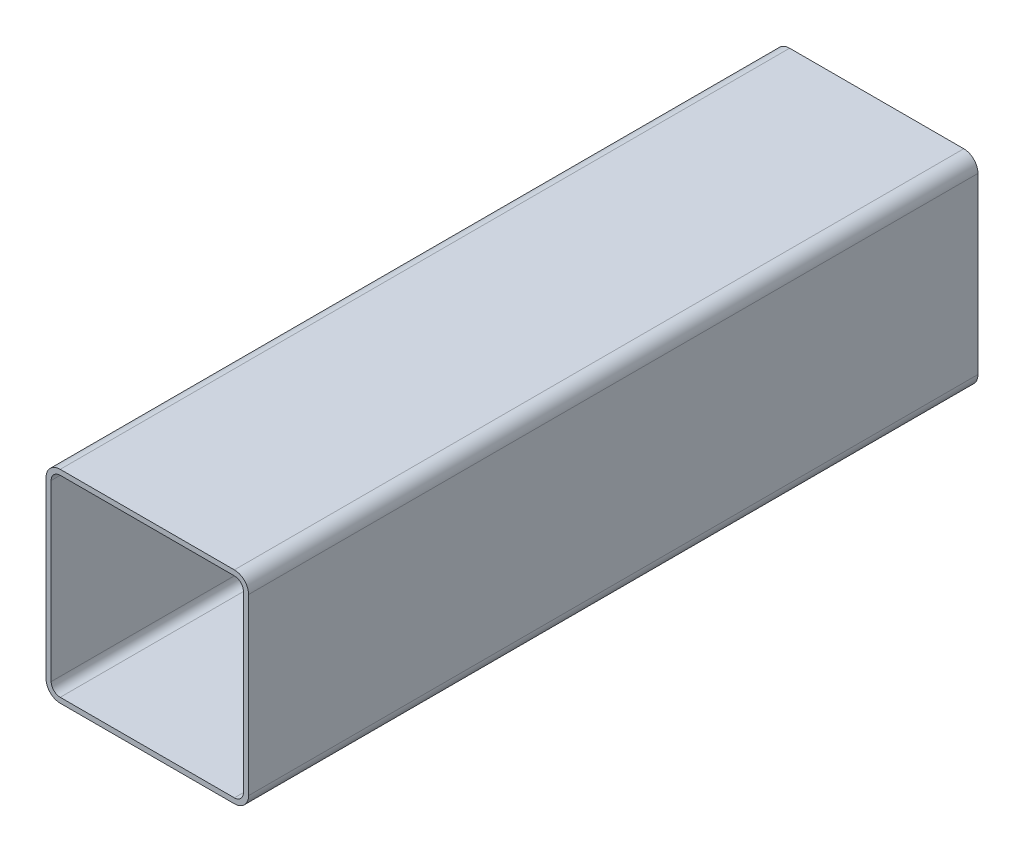
SolidWorks part; units mm, degrees
note: '?' marks a value the reader was unsure of.
material "Carbon Fiber, Plain Weave"
ref_plane "Front Plane" through (0, 0, 0) normal (0, 0, 1) x (1, 0, 0)
ref_plane "Top Plane" through (0, 0, 0) normal (0, 1, 0) x (1, 0, 0)
ref_plane "Right Plane" through (0, 0, 0) normal (1, 0, 0) x (0, 0, -1)
ref_axis "Axis1" through (0, 0, -88.99) along (0, 0, 1)?
ref_axis "Axis2" through (0, -55, 0) along (0, 1, 0)?
ref_axis "Axis3" through (-88.99, 0, 0) along (1, 0, 0)?
sketch "Sketch1" plane through (0, 0, 0) normal (0, 1, 0) x (1, 0, 0)
  line L0 (0, 0) -> (0, 304.8)
  dimension "D1" = 304.8
other "Structural Member1" corner treatment miter
ref_plane "Plane1" through (0, 0, 0) normal (0, 0, -1) x (-1, 0, 0)
sketch "Sketch137" plane through (0, 0, 0) normal (0, 0, -1) x (-1, 0, 0)
  line L0 (-42.3291, 36.3855) -> (-42.3291, -36.3855)
  line L1 (-36.3855, -42.3291) -> (36.3855, -42.3291)
  line L2 (-36.3855, 42.3291) -> (36.3855, 42.3291)
  line L3 (42.3291, 36.3855) -> (42.3291, -36.3855)
  line L4 (-42.3291, 42.3291) -> (42.3291, -42.3291) construction
  line L5 (-40.1701, 36.3855) -> (-40.1701, -36.3855)
  line L6 (-36.3855, -40.1701) -> (36.3855, -40.1701)
  line L7 (40.1701, 36.3855) -> (40.1701, -36.3855)
  line L8 (-36.3855, 40.1701) -> (36.3855, 40.1701)
  arc A0 (-42.3291, -36.3855) -> (-36.3855, -42.3291) centre (-36.3855, -36.3855) ccw
  arc A1 (36.3855, -42.3291) -> (42.3291, -36.3855) centre (36.3855, -36.3855) ccw
  arc A2 (36.3855, 42.3291) -> (42.3291, 36.3855) centre (36.3855, 36.3855) cw
  arc A3 (-42.3291, 36.3855) -> (-36.3855, 42.3291) centre (-36.3855, 36.3855) cw
  arc A4 (-40.1701, -36.3855) -> (-36.3855, -40.1701) centre (-36.3855, -36.3855) ccw
  arc A5 (36.3855, -40.1701) -> (40.1701, -36.3855) centre (36.3855, -36.3855) ccw
  arc A6 (36.3855, 40.1701) -> (40.1701, 36.3855) centre (36.3855, 36.3855) cw
  arc A7 (-40.1701, 36.3855) -> (-36.3855, 40.1701) centre (-36.3855, 36.3855) cw
  point P6 (-42.3291, -42.3291)
  point P28 (0, 0)
  dimension "CORNER_RADIUS" = 5.9436
  dimension "THICKNESS" = 2.159
  dimension "VERT LEG" = 84.6582
  dimension "HORZ LEG" = 84.6582
sketch "Sketch12" plane through (0, 42.3291, 0) normal (0, 1, 0) x (1, 0, 0)
  line L0 (0, 0) -> (0, 475) construction
  line L2 (-0.025, 436.65) -> (0.025, 436.65)
  line L3 (-3.2, 439.825) -> (-3.2, 510.175)
  line L4 (-0.025, 513.35) -> (0.025, 513.35)
  line L5 (3.2, 439.825) -> (3.2, 510.175)
  line L6 (-3.2, 436.65) -> (3.2, 513.35) construction
  line L7 (-3.2, 513.35) -> (3.2, 436.65) construction
  circle A0 centre (0, 475) radius 7.5 construction
  arc A1 (-0.025, 436.65) -> (-3.2, 439.825) centre (-0.025, 439.825) cw
  arc A2 (0.025, 436.65) -> (3.2, 439.825) centre (0.025, 439.825) ccw
  arc A3 (0.025, 513.35) -> (3.2, 510.175) centre (0.025, 510.175) cw
  arc A4 (-3.2, 510.175) -> (-0.025, 513.35) centre (-0.025, 510.175) cw
  dimension "D1" = 15
  dimension "D2" = 475
  dimension "D3" = 3.175
  dimension "D4" = 76.7
  dimension "D5" = 6.4
extrude "Cut-Extrude1" [suppressed] cut sketch "Sketch12" against normal up to next
hole_wizard "M5 Clearance Hole1" [suppressed] positions "Sketch14" profile "Sketch13" hole size "M5" standard "ANSI Metric"
sketch "Sketch14" plane through (42.3291, 0, 0) normal (-1, 0, 0) x (0, 0, 1)
  line L0 (0, 0) -> (-368.9375, 0) construction
  line L3 (-500, 21.8852) -> (-500, -22.8005) construction
  point P0 (-368.9375, 20)
  point P8 (-368.9375, -20)
  point P16 (-631.0625, -20)
  point P17 (-631.0625, 20)
  dimension "D1" = 40
  dimension "D2" = 500
  dimension "D3" = 262.125
sketch "Sketch13" plane through (42.3291, 20, -368.9375) normal (0, 1, 0) x (0, 0, -1)
  line L0 (0, 0) -> (0, 84.6582)
  line L1 (0, 84.6582) -> (2.75, 84.6582)
  line L2 (2.75, 84.6582) -> (2.75, 0)
  line L5 (2.75, 0) -> (0, 0)
  line L11 (0, -6.35) -> (0, 107.95) construction
  dimension "Thru Hole Dia." = 5.5
  dimension "Thru Hole Depth" = 84.6582
sketch "Sketch15" plane through (0, -42.3291, 0) normal (0, -1, 0) x (1, 0, 0)
  line L0 (0, -304.8) -> (0, -104.8) construction
  line L1 (36.3855, -304.8) -> (-36.3855, -304.8) construction
  line L3 (-0.025, -143.15) -> (0.025, -143.15)
  line L4 (-3.2, -139.975) -> (-3.2, -69.625)
  line L5 (-0.025, -66.45) -> (0.025, -66.45)
  line L6 (3.2, -139.975) -> (3.2, -69.625)
  line L7 (-3.2, -143.15) -> (3.2, -66.45) construction
  line L8 (-3.2, -66.45) -> (3.2, -143.15) construction
  circle A0 centre (0, -104.8) radius 7.5 construction
  arc A1 (-0.025, -143.15) -> (-3.2, -139.975) centre (-0.025, -139.975) cw
  arc A2 (0.025, -143.15) -> (3.2, -139.975) centre (0.025, -139.975) ccw
  arc A3 (0.025, -66.45) -> (3.2, -69.625) centre (0.025, -69.625) cw
  arc A4 (-3.2, -69.625) -> (-0.025, -66.45) centre (-0.025, -69.625) cw
  dimension "D1" = 15
  dimension "D3" = 3.175
  dimension "D2" = 200
  dimension "D4" = 6.4
  dimension "D5" = 76.7
extrude "Cut-Extrude2" [suppressed] cut sketch "Sketch15" against normal up to next
sketch "Sketch111" plane through (0, -42.3291, 0) normal (0, -1, 0) x (-1, 0, 0)
  line L0 (0, 65) -> (0, 0) construction
  line L1 (-11, 120) -> (11, 120)
  line L2 (-16, 115) -> (-16, 15)
  line L3 (-11, 10) -> (11, 10)
  line L4 (16, 115) -> (16, 15)
  line L5 (-16, 120) -> (16, 10) construction
  line L6 (-16, 10) -> (16, 120) construction
  arc A0 (11, 10) -> (16, 15) centre (11, 15) ccw
  arc A1 (-16, 15) -> (-11, 10) centre (-11, 15) ccw
  arc A2 (-11, 120) -> (-16, 115) centre (-11, 115) ccw
  arc A3 (11, 120) -> (16, 115) centre (11, 115) cw
  point P0 (0, 65)
  dimension "D4" = 5
  dimension "D1" = 65
  dimension "D2" = 32
  dimension "D3" = 110
extrude "Cut-Extrude3" [suppressed] cut sketch "Sketch111" against normal up to next
hole_wizard "M5 Clearance Hole2" [suppressed] positions "Sketch122" profile "Sketch121" hole size "M5" standard "ANSI Metric"
sketch "Sketch122" plane through (42.3291, 0, 0) normal (1, 0, 0) x (0, 0, -1)
  line L0 (0, 0) -> (28.3774, 0) construction
  line L3 (0, -36.3855) -> (0, 36.3855) construction
  point P0 (10, -27.5)
  point P11 (50, -27.5)
  point P13 (90, -27.5)
  point P16 (90, 27.5)
  point P17 (50, 27.5)
  point P18 (10, 27.5)
  dimension "D1" = 55
  dimension "D2" = 10
  dimension "D3" = 40
  dimension "D4" = 40
sketch "Sketch121" plane through (42.3291, -27.5, -10) normal (0, 1, 0) x (0, 0, -1)
  line L0 (0, 0) -> (0, 84.6582)
  line L1 (0, 84.6582) -> (2.75, 84.6582)
  line L2 (2.75, 84.6582) -> (2.75, 0)
  line L5 (2.75, 0) -> (0, 0)
  line L11 (0, -6.35) -> (0, 107.95) construction
  dimension "Thru Hole Dia." = 5.5
  dimension "Thru Hole Depth" = 84.6582
hole_wizard "M4 Clearance Hole1" [suppressed] positions "Sketch124" profile "Sketch123" hole size "M4" standard "ANSI Metric"
sketch "Sketch124" plane through (42.3291, 0, 0) normal (-1, 0, 0) x (0, 0, 1)
  line L0 (0, 0) -> (-36.75, 0) construction
  line L3 (0, -36.3855) -> (0, 36.3855) construction
  line L4 (-32.8, 0) -> (-32.8, 17.5) construction
  point P0 (-16.8, 17.5)
  point P14 (-16.8, -17.5)
  point P20 (-48.8, -17.5)
  point P21 (-48.8, 17.5)
  dimension "D1" = 16.8
  dimension "D2" = 35
  dimension "D3" = 32
sketch "Sketch123" plane through (42.3291, 17.5, -16.8) normal (0, 1, 0) x (0, 0, -1)
  line L0 (0, 0) -> (0, 84.6582)
  line L1 (0, 84.6582) -> (2.25, 84.6582)
  line L2 (2.25, 84.6582) -> (2.25, 0)
  line L5 (2.25, 0) -> (0, 0)
  line L11 (0, -6.35) -> (0, 107.95) construction
  dimension "Thru Hole Dia." = 4.5
  dimension "Thru Hole Depth" = 84.6582
hole_wizard "M5 Clearance Hole3" [suppressed] positions "Sketch126" profile "Sketch125" hole size "M5" standard "ANSI Metric"
sketch "Sketch126" plane through (42.3291, 0, 0) normal (-1, 0, 0) x (0, 0, 1)
  line L0 (-965, 34.2265) -> (-965, 0) construction
  line L2 (-965, 0) -> (-1000, 0) construction
  line L3 (-1000, -36.3855) -> (-1000, 36.3855) construction
  point P0 (-987.5, 22.5)
  point P14 (-987.5, -22.5)
  dimension "D2" = 45
  dimension "D3" = 12.5
sketch "Sketch125" plane through (42.3291, 22.5, -987.5) normal (0, 1, 0) x (0, 0, -1)
  line L0 (0, 0) -> (0, 84.6582)
  line L1 (0, 84.6582) -> (2.75, 84.6582)
  line L2 (2.75, 84.6582) -> (2.75, 0)
  line L5 (2.75, 0) -> (0, 0)
  line L11 (0, -6.35) -> (0, 107.95) construction
  dimension "Thru Hole Dia." = 5.5
  dimension "Thru Hole Depth" = 84.6582
sketch "Sketch127" [suppressed] plane through (0, 42.3291, 0) normal (0, 1, 0) x (1, 0, 0)
  line L0 (0, 0) -> (0, 127) construction
  line L1 (-3.4641, 132.5) -> (3.4641, 132.5)
  circle A0 centre (0, 127) radius 6.5
  dimension "D1" = 13
  dimension "D2" = 12
  dimension "D3" = 127
extrude "Cut-Extrude5" [suppressed] cut sketch "Sketch127" against normal blind 10
hole_wizard "M5 Clearance Hole4" [suppressed] positions "Sketch129" profile "Sketch128" hole size "M5" standard "ANSI Metric"
sketch "Sketch129" plane through (42.3291, 0, 0) normal (-1, 0, 0) x (0, 0, 1)
  line L0 (-525, 0) -> (-502.2097, 0) construction
  line L1 (-525, -36.3855) -> (-525, 36.3855) construction
  point P0 (-518.65, 25)
  point P10 (-518.65, -25)
  dimension "D1" = 6.35
  dimension "D2" = 50
sketch "Sketch128" plane through (42.3291, 25, -518.65) normal (0, 1, 0) x (0, 0, -1)
  line L0 (0, 0) -> (0, 84.6582)
  line L1 (0, 84.6582) -> (2.75, 84.6582)
  line L2 (2.75, 84.6582) -> (2.75, 0)
  line L5 (2.75, 0) -> (0, 0)
  line L11 (0, -6.35) -> (0, 107.95) construction
  dimension "Thru Hole Dia." = 5.5
  dimension "Thru Hole Depth" = 84.6582
hole_wizard "M4 Clearance Hole2" [suppressed] positions "Sketch141" profile "Sketch140" hole size "M4" standard "ANSI Metric"
sketch "Sketch141" plane through (0, 26.67, 0) normal (0, 1, 0) x (1, 0, 0)
  line L0 (0, 550) -> (0, 0) construction
  line L1 (-22.7012, 550) -> (22.7013, 550) construction
  line L3 (-7.5, 545) -> (7.5, 545) construction
  line L5 (0, 275) -> (26.67, 275) construction
  line L6 (26.67, 550) -> (26.67, 0) construction
  point P0 (-7.5, 545)
  point P2 (7.5, 545)
  point P16 (0, 545)
  point P24 (7.5, 5)
  point P25 (-7.5, 5)
  dimension "D1" = 5
  dimension "D2" = 15
sketch "Sketch140" plane through (-7.5, 26.67, -545) normal (1, 0, 0) x (0, 0, 1)
  line L0 (0, 0) -> (0, 53.34)
  line L1 (0, 53.34) -> (2.25, 53.34)
  line L2 (2.25, 53.34) -> (2.25, 0)
  line L5 (2.25, 0) -> (0, 0)
  line L11 (0, -6.35) -> (0, 107.95) construction
  dimension "Thru Hole Dia." = 4.5
  dimension "Thru Hole Depth" = 53.34
hole_wizard "M5 Clearance Hole5" [suppressed] positions "Sketch143" profile "Sketch142" hole size "M5" standard "ANSI Metric"
sketch "Sketch143" plane through (-26.67, 0, 0) normal (-1, 0, 0) x (0, 0, 1)
  line L0 (0, 11.33) -> (-15, 11.33) construction
  line L1 (0, -22.7013) -> (0, 22.7012) construction
  point P0 (-112, 11.33)
  point P2 (-79.6667, 11.33)
  point P4 (-47.3333, 11.33)
  point P6 (-15, 11.33)
  dimension "D1" = 11.33
  dimension "D2" = 15
  dimension "D3" = 47.3333
  dimension "D4" = 79.6667
  dimension "D5" = 112
sketch "Sketch142" plane through (-26.67, 11.33, -112) normal (0, 1, 0) x (0, 0, 1)
  line L0 (0, 0) -> (0, 53.34)
  line L1 (0, 53.34) -> (2.75, 53.34)
  line L2 (2.75, 53.34) -> (2.75, 0)
  line L5 (2.75, 0) -> (0, 0)
  line L11 (0, -6.35) -> (0, 107.95) construction
  dimension "Thru Hole Dia." = 5.5
  dimension "Thru Hole Depth" = 53.34
sketch "Sketch144" [suppressed] plane through (0, -26.67, 0) normal (0, -1, 0) x (1, 0, 0)
  line L0 (0, 0) -> (0, -15) construction
  line L1 (-11.67, -15) -> (11.67, -15)
  line L2 (-11.67, -15) -> (-11.67, -120)
  line L3 (-11.67, -120) -> (11.67, -120)
  line L4 (11.67, -15) -> (11.67, -120)
  line L5 (-26.67, -550) -> (-26.67, 0) construction
  line L6 (22.7012, 0) -> (-22.7012, 0) construction
  dimension "D1" = 15
  dimension "D2" = 15
  dimension "D3" = 120
extrude "Cut-Extrude6" [suppressed] cut sketch "Sketch144" against normal up to next
equation "\"D3@Sketch15\"=\"D3@Sketch12\""
equation "\"D4@Sketch15\"=\"D5@Sketch12\""
equation "\"D5@Sketch15\"=\"D4@Sketch12\""
